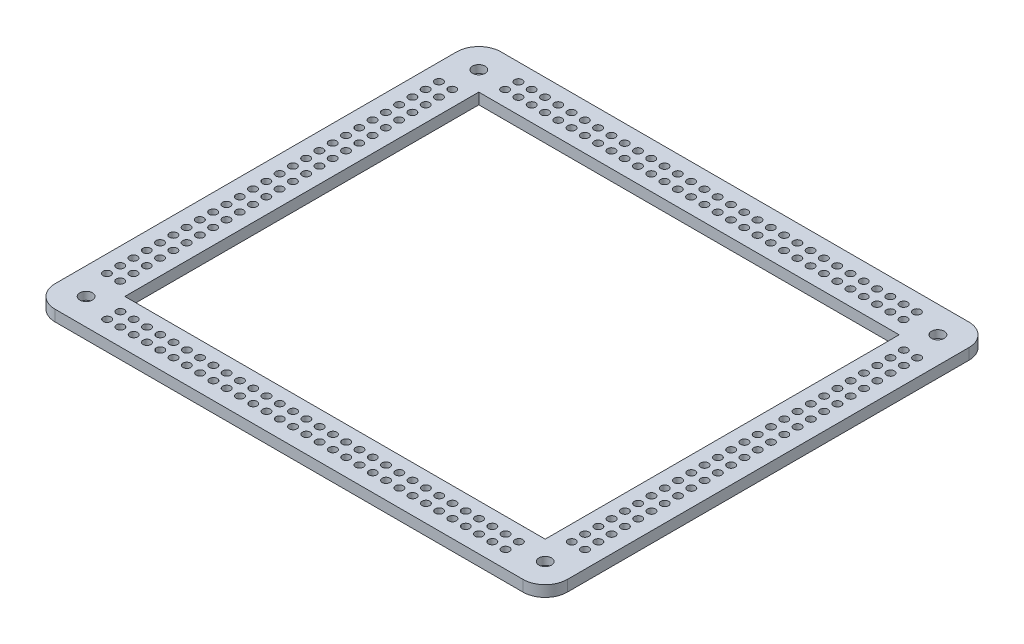
SolidWorks part; units mm, degrees
ref_plane "Front Plane" through (0, 0, 0) normal (0, 0, 1) x (1, 0, 0)
ref_plane "Top Plane" through (0, 0, 0) normal (0, 1, 0) x (1, 0, 0)
ref_plane "Right Plane" through (0, 0, 0) normal (1, 0, 0) x (0, 0, -1)
sketch "Sketch1" plane through (0, 0, 0) normal (0, 1, 0) x (1, 0, 0)
  line L1 (-94.95, 79.95) -> (94.95, 79.95)
  line L2 (-94.95, 79.95) -> (-94.95, -79.95)
  line L3 (-94.95, -79.95) -> (94.95, -79.95)
  line L4 (94.95, 79.95) -> (94.95, -79.95)
  line L5 (-115.7, 100.7) -> (115.7, 100.7)
  line L6 (-115.7, 100.7) -> (-115.7, -100.7)
  line L7 (-115.7, -100.7) -> (115.7, -100.7)
  line L8 (115.7, 100.7) -> (115.7, -100.7)
  point P4 (-94.95, 0)
  point P6 (0, 79.95)
  point P11 (0, -100.7)
  point P12 (-115.7, 0)
  dimension "D1" = 189.9
  dimension "D2" = 159.9
  dimension "D3" = 20.75
  dimension "D4" = 20.75
extrude "Boss-Extrude1" add sketch "Sketch1" along normal blind 5
fillet "Fillet1" radius 10 4 edges at (-115.7, 2.5, -100.7) (115.7, 2.5, -100.7) (115.7, 2.5, 100.7) (-115.7, 2.5, 100.7)
sketch "Sketch2" plane through (0, 0, 0) normal (0, -1, 0) x (1, 0, 0)
  line L0 (-105.7, 100.7) -> (105.7, 100.7) construction
  line L1 (-115.7, -90.7) -> (-115.7, 90.7) construction
  circle A0 centre (-103.7, 88.7) radius 5.85
  dimension "D3" = 11.7
  dimension "D1" = 12
  dimension "D2" = 12
extrude "Boss-Extrude2" add sketch "Sketch2" along normal blind 2.5
sketch "Sketch3" plane through (0, 5, 0) normal (0, 1, 0) x (1, 0, 0)
  line L2 (-115.7, 90.7) -> (-115.7, -90.7) construction
  line L3 (-105.7, -100.7) -> (105.7, -100.7) construction
  circle A0 centre (-103.7, -88.7) radius 1.55
  dimension "D1" = 3.1
  dimension "D2" = 12
  dimension "D3" = 12
extrude "Cut-Extrude1" cut sketch "Sketch3" against normal blind 7.5
sketch "Sketch4" plane through (0, 5, 0) normal (0, 1, 0) x (1, 0, 0)
  circle A0 centre (-103.7, -88.7) radius 2.85
  dimension "D1" = 5.7
extrude "Cut-Extrude2" cut sketch "Sketch4" against normal blind 3.5
mirror "Mirror3" about plane through (0, 0, 0) normal (1, 0, 0) of "Cut-Extrude1", "Cut-Extrude2", "Boss-Extrude2"
mirror "Mirror4" about plane through (0, 0, 0) normal (0, 0, 1) of "Mirror3"
sketch "Sketch5" plane through (0, 5, 0) normal (0, 1, 0) x (1, 0, 0)
  line L0 (-94.95, -79.95) -> (94.95, -79.95) construction
  line L1 (-115.7, 90.7) -> (-115.7, -90.7) construction
  circle A0 centre (-90, -86.9) radius 1.75
  circle A1 centre (-90, -92.9) radius 1.75
  circle A4 centre (-84, -86.9) radius 1.75
  circle A5 centre (-84, -92.9) radius 1.75
  circle A7 centre (-78, -86.9) radius 1.75
  circle A8 centre (-78, -92.9) radius 1.75
  circle A10 centre (-72, -86.9) radius 1.75
  circle A11 centre (-72, -92.9) radius 1.75
  circle A13 centre (-66, -86.9) radius 1.75
  circle A14 centre (-66, -92.9) radius 1.75
  circle A16 centre (-60, -86.9) radius 1.75
  circle A17 centre (-60, -92.9) radius 1.75
  circle A19 centre (-54, -86.9) radius 1.75
  circle A20 centre (-54, -92.9) radius 1.75
  circle A22 centre (-48, -86.9) radius 1.75
  circle A23 centre (-48, -92.9) radius 1.75
  circle A25 centre (-42, -86.9) radius 1.75
  circle A26 centre (-42, -92.9) radius 1.75
  circle A28 centre (-36, -86.9) radius 1.75
  circle A29 centre (-36, -92.9) radius 1.75
  circle A31 centre (-30, -86.9) radius 1.75
  circle A32 centre (-30, -92.9) radius 1.75
  circle A34 centre (-24, -86.9) radius 1.75
  circle A35 centre (-24, -92.9) radius 1.75
  circle A37 centre (-18, -86.9) radius 1.75
  circle A38 centre (-18, -92.9) radius 1.75
  circle A40 centre (-12, -86.9) radius 1.75
  circle A41 centre (-12, -92.9) radius 1.75
  circle A43 centre (-6, -86.9) radius 1.75
  circle A44 centre (-6, -92.9) radius 1.75
  circle A46 centre (0, -86.9) radius 1.75
  circle A47 centre (0, -92.9) radius 1.75
  circle A49 centre (6, -86.9) radius 1.75
  circle A50 centre (6, -92.9) radius 1.75
  circle A52 centre (12, -86.9) radius 1.75
  circle A53 centre (12, -92.9) radius 1.75
  circle A55 centre (18, -86.9) radius 1.75
  circle A56 centre (18, -92.9) radius 1.75
  circle A58 centre (24, -86.9) radius 1.75
  circle A59 centre (24, -92.9) radius 1.75
  circle A61 centre (30, -86.9) radius 1.75
  circle A62 centre (30, -92.9) radius 1.75
  circle A64 centre (36, -86.9) radius 1.75
  circle A65 centre (36, -92.9) radius 1.75
  circle A67 centre (42, -86.9) radius 1.75
  circle A68 centre (42, -92.9) radius 1.75
  circle A70 centre (48, -86.9) radius 1.75
  circle A71 centre (48, -92.9) radius 1.75
  circle A73 centre (54, -86.9) radius 1.75
  circle A74 centre (54, -92.9) radius 1.75
  circle A76 centre (60, -86.9) radius 1.75
  circle A77 centre (60, -92.9) radius 1.75
  circle A79 centre (66, -86.9) radius 1.75
  circle A80 centre (66, -92.9) radius 1.75
  circle A82 centre (72, -86.9) radius 1.75
  circle A83 centre (72, -92.9) radius 1.75
  circle A85 centre (78, -86.9) radius 1.75
  circle A86 centre (78, -92.9) radius 1.75
  circle A88 centre (84, -86.9) radius 1.75
  circle A89 centre (84, -92.9) radius 1.75
  circle A91 centre (90, -86.9) radius 1.75
  circle A92 centre (90, -92.9) radius 1.75
  circle A135 centre (108, -86.9) radius 1.75 [skipped]
  circle A136 centre (108, -92.9) radius 1.75 [skipped]
  circle A137 centre (102, -86.9) radius 1.75 [skipped]
  circle A138 centre (102, -92.9) radius 1.75 [skipped]
  circle A139 centre (96, -86.9) radius 1.75 [skipped]
  circle A140 centre (96, -92.9) radius 1.75 [skipped]
  dimension "D1" = 3.5
  dimension "D4" = 6
  dimension "D2" = 25.7
  dimension "D3" = 6
  dimension "D5" = 6.95
  dimension "D6" = 34
extrude "Cut-Extrude3" cut sketch "Sketch5" against normal blind 5
mirror "Mirror5" about plane through (0, 0, 0) normal (0, 0, 1) of "Cut-Extrude3"
sketch "Sketch6" plane through (0, 5, 0) normal (0, 1, 0) x (1, 0, 0)
  line L1 (-115.7, 90.7) -> (-115.7, -90.7) construction
  circle A1 centre (-102, -75) radius 1.75
  circle A2 centre (-108, -75) radius 1.75
  circle A3 centre (-103.7, -88.7) radius 2.85 construction
  circle A5 centre (-102, -69) radius 1.75
  circle A6 centre (-108, -69) radius 1.75
  circle A8 centre (-102, -63) radius 1.75
  circle A9 centre (-108, -63) radius 1.75
  circle A11 centre (-102, -57) radius 1.75
  circle A12 centre (-108, -57) radius 1.75
  circle A14 centre (-102, -51) radius 1.75
  circle A15 centre (-108, -51) radius 1.75
  circle A17 centre (-102, -45) radius 1.75
  circle A18 centre (-108, -45) radius 1.75
  circle A20 centre (-102, -39) radius 1.75
  circle A21 centre (-108, -39) radius 1.75
  circle A23 centre (-102, -33) radius 1.75
  circle A24 centre (-108, -33) radius 1.75
  circle A26 centre (-102, -27) radius 1.75
  circle A27 centre (-108, -27) radius 1.75
  circle A29 centre (-102, -21) radius 1.75
  circle A30 centre (-108, -21) radius 1.75
  circle A32 centre (-102, -15) radius 1.75
  circle A33 centre (-108, -15) radius 1.75
  circle A35 centre (-102, -9) radius 1.75
  circle A36 centre (-108, -9) radius 1.75
  circle A38 centre (-102, -3) radius 1.75
  circle A39 centre (-108, -3) radius 1.75
  circle A41 centre (-102, 3) radius 1.75
  circle A42 centre (-108, 3) radius 1.75
  circle A44 centre (-102, 9) radius 1.75
  circle A45 centre (-108, 9) radius 1.75
  circle A47 centre (-102, 15) radius 1.75
  circle A48 centre (-108, 15) radius 1.75
  circle A50 centre (-102, 21) radius 1.75
  circle A51 centre (-108, 21) radius 1.75
  circle A53 centre (-102, 27) radius 1.75
  circle A54 centre (-108, 27) radius 1.75
  circle A56 centre (-102, 33) radius 1.75
  circle A57 centre (-108, 33) radius 1.75
  circle A59 centre (-102, 39) radius 1.75
  circle A60 centre (-108, 39) radius 1.75
  circle A62 centre (-102, 45) radius 1.75
  circle A63 centre (-108, 45) radius 1.75
  circle A65 centre (-102, 51) radius 1.75
  circle A66 centre (-108, 51) radius 1.75
  circle A68 centre (-102, 57) radius 1.75
  circle A69 centre (-108, 57) radius 1.75
  circle A71 centre (-102, 63) radius 1.75
  circle A72 centre (-108, 63) radius 1.75
  circle A74 centre (-102, 69) radius 1.75
  circle A75 centre (-108, 69) radius 1.75
  circle A77 centre (-102, 75) radius 1.75
  circle A78 centre (-108, 75) radius 1.75
  circle A116 centre (-102, 93) radius 1.75 [skipped]
  circle A117 centre (-108, 93) radius 1.75 [skipped]
  circle A118 centre (-102, 87) radius 1.75 [skipped]
  circle A119 centre (-108, 87) radius 1.75 [skipped]
  circle A120 centre (-102, 81) radius 1.75 [skipped]
  circle A121 centre (-108, 81) radius 1.75 [skipped]
  dimension "D4" = 13.7
  dimension "D1" = 7.7
  dimension "D2" = 6
  dimension "D7" = 29
extrude "Cut-Extrude4" cut sketch "Sketch6" against normal blind 5
mirror "Mirror6" about plane through (0, 0, 0) normal (1, 0, 0) of "Cut-Extrude4"
